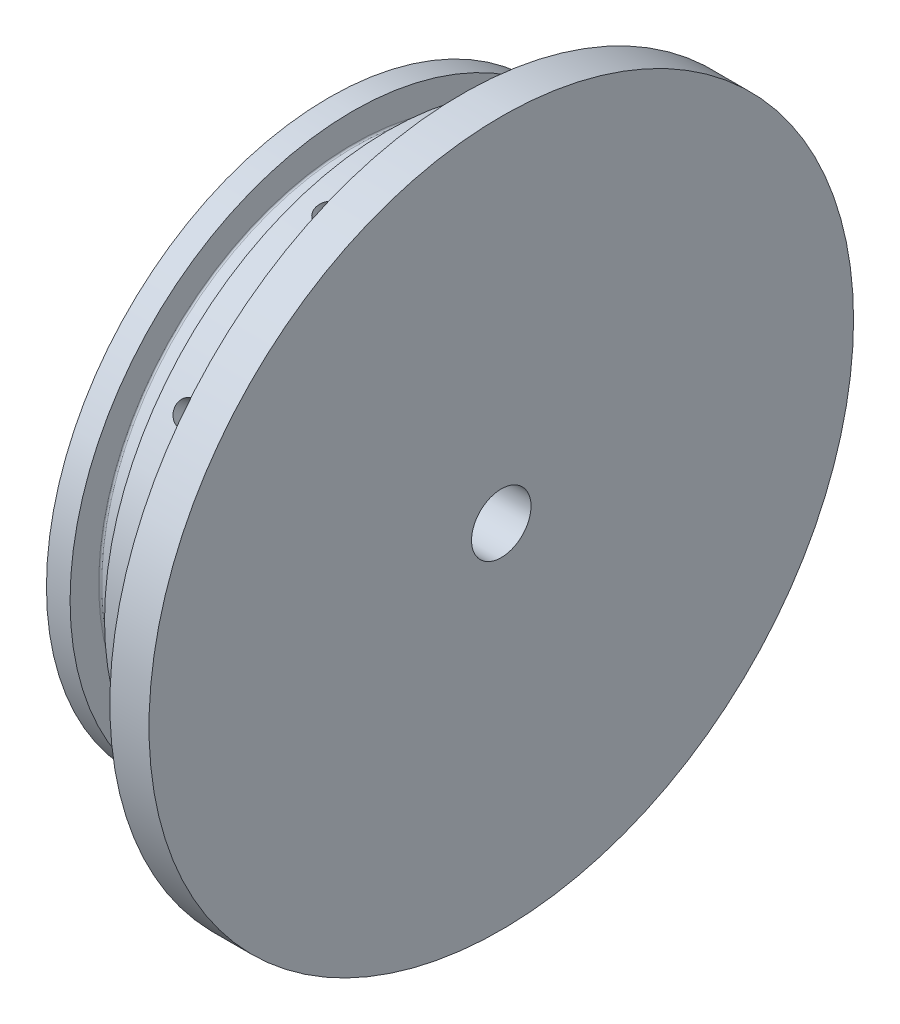
SolidWorks part; units mm, degrees
material "7075-T6 (SN)"
ref_plane "Front Plane" through (0, 0, 0) normal (0, 0, 1) x (1, 0, 0)
ref_plane "Top Plane" through (0, 0, 0) normal (0, 1, 0) x (1, 0, 0)
ref_plane "Right Plane" through (0, 0, 0) normal (1, 0, 0) x (0, 0, -1)
sketch "Sketch1" plane through (0, 0, 0) normal (1, 0, 0) x (0, 0, -1)
  circle A0 centre (0, 0) radius 57.15
  dimension "D1" = 114.3
extrude "Boss-Extrude1" add sketch "Sketch1" along normal blind 6.35
sketch "Sketch2" plane through (0, 0, 0) normal (-1, 0, 0) x (0, 0, 1)
  circle A0 centre (0, 0) radius 45.847
  dimension "D1" = 91.694
extrude "Boss-Extrude2" add sketch "Sketch2" along normal blind 21.59
sketch "Sketch3" plane through (-21.59, 0, 0) normal (-1, 0, 0) x (0, 0, 1)
  circle A0 centre (0, 0) radius 34.925
  dimension "D1" = 69.85
extrude "Cut-Extrude1" cut sketch "Sketch3" against normal blind 6.35
sketch "Sketch10" plane through (0, 0, 0) normal (0, 1, 0) x (1, 0, 0)
  line L0 (0, 0) -> (-53.2238, 0) construction
  line L1 (-26.2636, 0) -> (26.2636, 0) construction
  line L2 (0, 0) -> (0, 64.5447) construction
  line L3 (0, -62.865) -> (0, 62.865) construction
ref_plane "Plane1" through (0, 0, -45.847) normal (0, 0, -1) x (-1, 0, 0)
sketch "Sketch11" plane through (0, 0, -45.847) normal (0, 0, -1) x (-1, 0, 0)
  line L0 (0, 0) -> (53.2238, 0) construction
  line L1 (0, -45.847) -> (0, 45.847) construction
  circle A0 centre (7.62, 0) radius 1.8986
  dimension "D2" = 3.7973
  dimension "D1" = 7.62
extrude "Cut-Extrude3" cut sketch "Sketch11" against normal blind 10.16
pattern_circular "CirPattern1" count 10 every 36 about axis through (0, 0, 0) along (-1, 0, 0) of "Cut-Extrude3" reverse direction yes
sketch "Sketch13" plane through (0, 0, 0) normal (0, 0, 1) x (1, 0, 0)
  line L0 (-21.59, 0) -> (-21.59, 45.847) construction
  line L1 (-21.59, 34.925) -> (-21.59, -34.925) construction
  line L2 (-21.59, 45.847) -> (0, 45.847) construction
  line L3 (0, 45.847) -> (0, -45.847) construction
  line L4 (0, 0) -> (-64.5609, 0) construction
  line L5 (-17.7575, 45.847) -> (-12.1695, 45.847)
  line L6 (-17.7575, 45.847) -> (-17.7575, 41.2115)
  line L7 (-17.5035, 40.9575) -> (-12.4235, 40.9575)
  line L8 (-12.1695, 45.847) -> (-12.1695, 41.2115)
  arc A0 (-12.4235, 40.9575) -> (-12.1695, 41.2115) centre (-12.4235, 41.2115) ccw
  arc A1 (-17.5035, 40.9575) -> (-17.7575, 41.2115) centre (-17.5035, 41.2115) cw
  point P13 (-12.1695, 40.9575)
  point P16 (-17.7575, 40.9575)
  dimension "D4" = 0.254
  dimension "D1" = 45.847
  dimension "D2" = 5.588
  dimension "D3" = 40.9575
revolve "Cut-Revolve3" cut sketch "Sketch13" angle 360 about L4
sketch "Sketch15" plane through (6.35, 0, 0) normal (1, 0, 0) x (0, 0, -1)
  circle A0 centre (0, 0) radius 4.826
  dimension "D1" = 9.652
extrude "Cut-Extrude4" cut sketch "Sketch15" against normal through all
